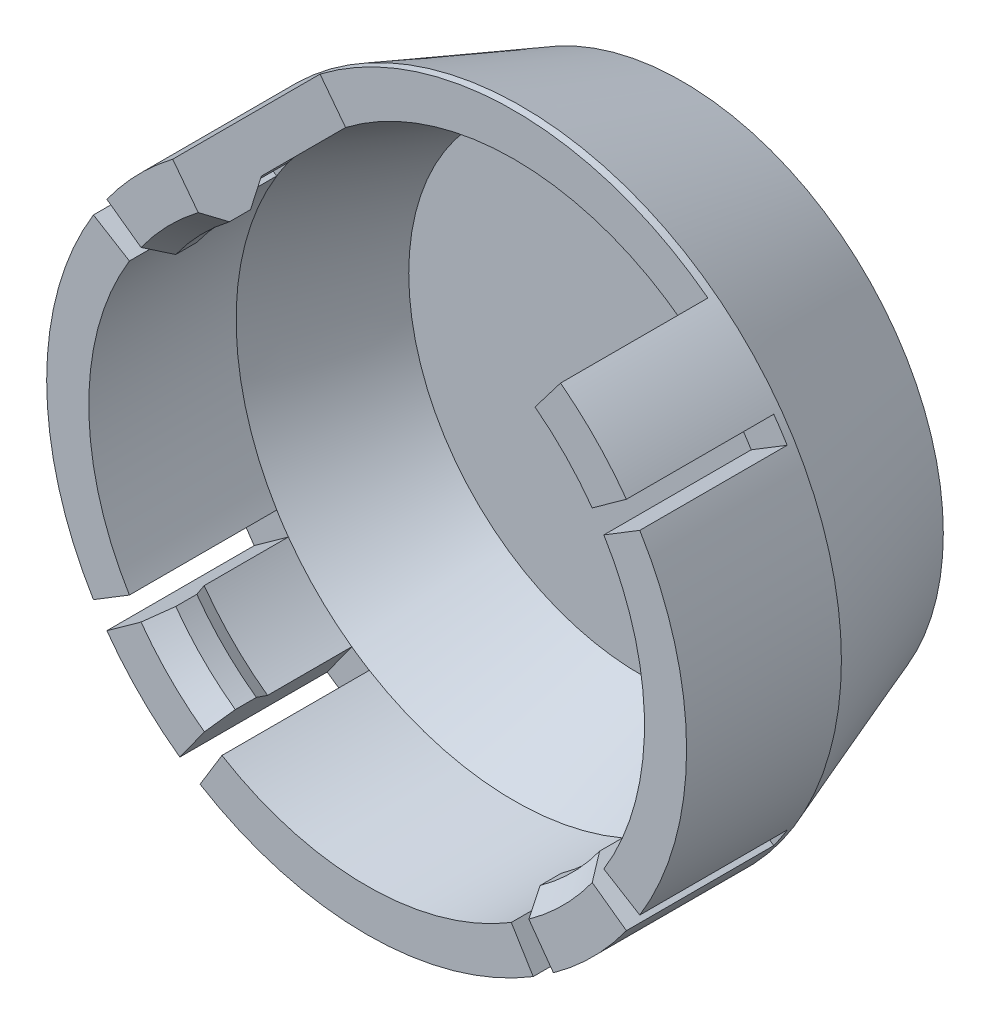
SolidWorks part; units mm, degrees
ref_plane "Front Plane" through (0, 0, 0) normal (0, 0, 1) x (1, 0, 0)
ref_plane "Top Plane" through (0, 0, 0) normal (0, 1, 0) x (1, 0, 0)
ref_plane "Right Plane" through (0, 0, 0) normal (1, 0, 0) x (0, 0, -1)
sketch "Sketch1" plane through (0, 0, 0) normal (1, 0, 0) x (0, 0, -1)
  line L0 (0, 15.2) -> (7.3551, 15.2)
  line L1 (7.3551, 15.2) -> (15, 12.3969)
  line L2 (15, 12.3969) -> (15, 0)
  line L3 (13, 0) -> (15, 0)
  line L4 (2, 12.4) -> (1, 12.4)
  line L5 (2, 12.4) -> (3, 13.2)
  line L6 (13, 0) -> (13, 11)
  line L7 (13, 11) -> (7, 13.2)
  line L8 (7, 13.2) -> (3, 13.2)
  line L9 (0, 13.2) -> (0, 15.2)
  line L10 (1, 12.4) -> (0, 13.2)
  dimension "D1" = 11
  dimension "D2" = 13.2
  dimension "D3" = 13
  dimension "D4" = 1
  dimension "D5" = 2
  dimension "D6" = 2
  dimension "D7" = 7
  dimension "D8" = 3
  dimension "D9" = 0.8
revolve "Revolve1" add sketch "Sketch1" angle 360 about L3
sketch "Sketch2" plane through (0, 0, 0) normal (0, 0, 1) x (1, 0, 0)
  line L0 (-7.5152, 9.8632) -> (0, 0) construction
  line L1 (-11.5815, 15.2) -> (11.5815, 15.2)
  line L2 (-11.5815, 15.2) -> (-7.5152, 9.8632)
  line L3 (-7.5152, 9.8632) -> (7.5152, 9.8632)
  line L4 (11.5815, 15.2) -> (7.5152, 9.8632)
  line L5 (0, 0) -> (7.5152, 9.8632) construction
  line L6 (-8, 10.4995) -> (8, 10.4995) construction
  circle A0 centre (0, 0) radius 12.4 construction
  circle A1 centre (0, 0) radius 15.2 construction
  circle A3 centre (0, 0) radius 13.2 construction
  dimension "D1" = 16
extrude "Cut-Extrude1" cut sketch "Sketch2" against normal blind 7
sketch "Sketch3" plane through (0, 0, 0) normal (0, 0, 1) x (1, 0, 0)
  line L0 (-8.8737, 12.3409) -> (-7.2391, 10.0675)
  line L1 (-7.2391, 10.0675) -> (-10.0675, 7.2391)
  line L2 (-10.0675, 7.2391) -> (-12.3409, 8.8737)
  line L3 (-7.914, 12.9772) -> (-6.8727, 11.2697)
  line L4 (-12.9776, 7.9133) -> (-11.2701, 6.8721)
  line L5 (-11.2701, 6.8721) -> (-10.6863, 7.684) construction
  line L6 (0, 0) -> (0, 13.2)
  line L7 (-6.8727, 11.2697) -> (-7.7061, 10.7171) construction
  line L8 (-13.2, 0) -> (0, 0)
  line L11 (0, 0) -> (-12.6174, 12.6174) construction
  line L12 (-11.2701, 6.8721) -> (0, 0) construction
  line L14 (-10.0675, 7.2391) -> (0, 0) construction
  line L15 (-7.2391, 10.0675) -> (0, 0) construction
  line L17 (-6.8727, 11.2697) -> (0.0164, -0.027) construction
  arc A0 (-8.8737, 12.3409) -> (-7.914, 12.9772) centre (0, 0) cw
  arc A1 (-6.8727, 11.2697) -> (0, 13.2) centre (0, 0) cw
  arc A2 (-12.3409, 8.8737) -> (-12.9776, 7.9133) centre (0, 0) ccw
  arc A3 (-11.2701, 6.8721) -> (-13.2, 0) centre (0, 0) ccw
  arc A4 (-8, 10.4995) -> (8, 10.4995) centre (0, 0) ccw construction
  arc A5 (8, 10.4995) -> (-8, 10.4995) centre (0, 0) ccw construction
  arc A6 (-9.2121, 12.0904) -> (9.2121, 12.0904) centre (0, 0) ccw construction
  arc A8 (-7.5152, 9.8632) -> (7.5152, 9.8632) centre (0, 0) ccw construction
  arc A9 (9.2121, 12.0904) -> (-9.2121, 12.0904) centre (0, 0) ccw construction
  dimension "D1" = 45
  dimension "D2" = 2
  dimension "D3" = 4
  dimension "D4" = 1
extrude "Cut-Extrude2" cut sketch "Sketch3" against normal up to surface (7 mm away) up to face at (0, 12.7475, -7)
pattern_circular "CirPattern1" count 4 over 360 about axis through (0, 0, 0) along (0, 0, 1) of "Cut-Extrude2"
